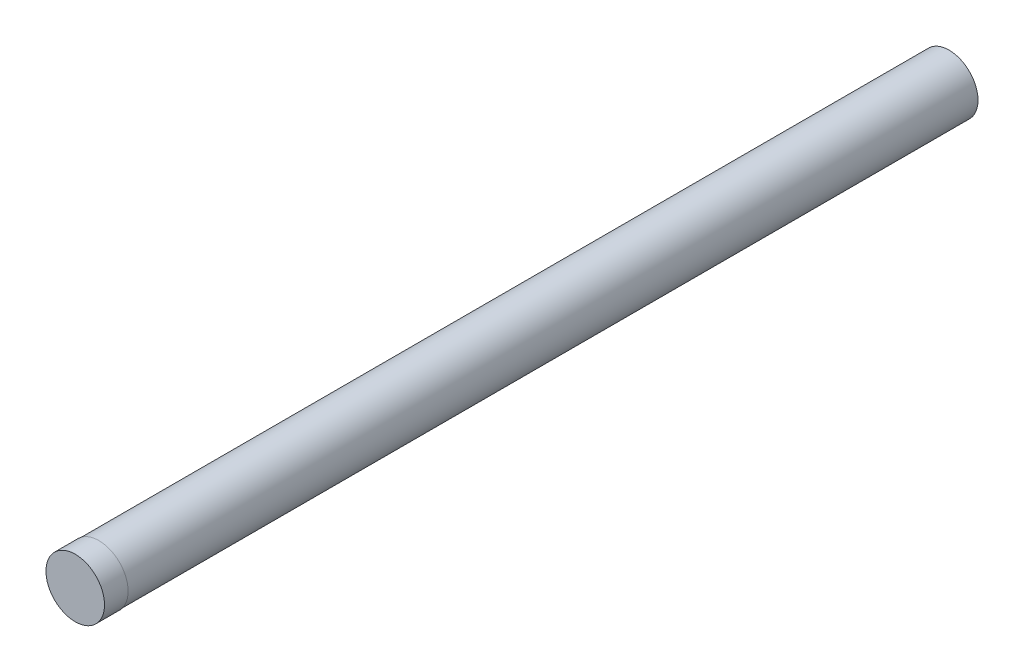
SolidWorks part; units mm, degrees
ref_plane "Front Plane" through (0, 0, 0) normal (0, 0, 1) x (1, 0, 0)
ref_plane "Top Plane" through (0, 0, 0) normal (0, 1, 0) x (1, 0, 0)
ref_plane "Right Plane" through (0, 0, 0) normal (1, 0, 0) x (0, 0, -1)
sketch "Sketch1" plane through (0, 0, 0) normal (0, 0, 1) x (1, 0, 0)
  circle A0 centre (0, 0) radius 2.45
  dimension "D1" = 4.9
extrude "Boss-Extrude1" add sketch "Sketch1" along normal blind 10 and the other way blind 64
sketch "Sketch2" plane through (0, 0, 0) normal (0, 0, 1) x (1, 0, 0)
  circle A0 centre (0, 0) radius 2.5 construction
  dimension "D1" = 5
sketch "Sketch3" plane through (0, 0, 10) normal (0, 0, 1) x (1, 0, 0)
  circle A0 centre (0, 0) radius 2.48
  dimension "D1" = 4.96
extrude "Boss-Extrude2" add sketch "Sketch3" against normal blind 2
